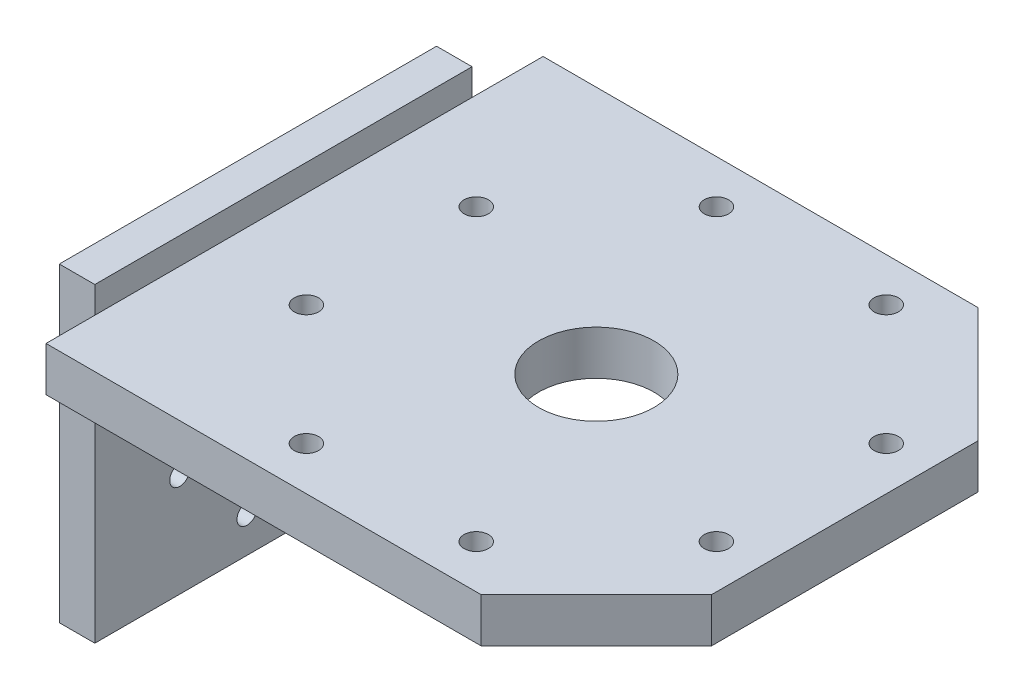
SolidWorks part; units mm, degrees
material "6061-T6 (SS)"
ref_plane "Front Plane" through (0, 0, 0) normal (0, 0, 1) x (1, 0, 0)
ref_plane "Top Plane" through (0, 0, 0) normal (0, 1, 0) x (1, 0, 0)
ref_plane "Right Plane" through (0, 0, 0) normal (1, 0, 0) x (0, 0, -1)
ref_plane "PL_Back_Plate_base" through (-76, 0, 0) normal (1, 0, 0) x (0, 0, -1)
sketch "SK_Back_Plate" plane through (-76, 0, 0) normal (1, 0, 0) x (0, 0, -1)
  line L0 (40, 36) -> (40, -34)
  line L1 (40, -34) -> (-45, -34)
  line L2 (-45, -34) -> (-45, 36)
  line L3 (-45, 36) -> (40, 36)
  circle A0 centre (25.8686, -10.7151) radius 2.25
  circle A1 centre (10.7151, -25.8686) radius 2.25
  circle A2 centre (-10.7151, -25.8686) radius 2.25
  circle A3 centre (-25.8686, -10.7151) radius 2.25
  circle A4 centre (-25.8686, 10.7151) radius 2.25
  circle A5 centre (-10.7151, 25.8686) radius 2.25
  circle A6 centre (10.7151, 25.8686) radius 2.25
  circle A7 centre (25.8686, 10.7151) radius 2.25
  circle A8 centre (0, 0) radius 6
  dimension "D9_SK_Back_Plate" = 4.5
  dimension "D12_SK_Back_Plate" = 4.5
  dimension "D15_SK_Back_Plate" = 4.5
  dimension "D18_SK_Back_Plate" = 4.5
  dimension "D21_SK_Back_Plate" = 4.5
  dimension "D24_SK_Back_Plate" = 4.5
  dimension "D27_SK_Back_Plate" = 4.5
  dimension "D30_SK_Back_Plate" = 4.5
  dimension "D33_SK_Back_Plate" = 12
  dimension "P1" = 40
  dimension "P2" = 36
  dimension "P3" = 40
  dimension "P4" = 34
  dimension "P5" = 45
  dimension "P6" = 34
  dimension "P7" = 45
  dimension "P8" = 36
  dimension "P10" = 25.8686
  dimension "P11" = 10.7151
  dimension "P13" = 10.7151
  dimension "P14" = 25.8686
  dimension "P16" = 10.7151
  dimension "P17" = 25.8686
  dimension "P19" = 25.8686
  dimension "P20" = 10.7151
  dimension "P22" = 25.8686
  dimension "P23" = 10.7151
  dimension "P25" = 10.7151
  dimension "P26" = 25.8686
  dimension "P28" = 10.7151
  dimension "P29" = 25.8686
  dimension "P31" = 25.8686
  dimension "P32" = 10.7151
extrude "Back_Plate" add sketch "SK_Back_Plate" along normal blind 8
ref_plane "PL_Roll_Pilot_Recess_base" through (-76, 0, 0) normal (1, 0, 0) x (0, 0, -1)
sketch "SK_Roll_Pilot_Recess" plane through (-76, 0, 0) normal (1, 0, 0) x (0, 0, -1)
  circle A0 centre (0, 0) radius 22.15
  dimension "D1_SK_Roll_Pilot_Recess" = 44.3
extrude "Roll_Pilot_Recess" cut sketch "SK_Roll_Pilot_Recess" along normal blind 2.2
ref_plane "PL_Medial_Plate_base" through (0, 20, 0) normal (0, 1, 0) x (1, 0, 0)
sketch "SK_Medial_Plate" plane through (0, 20, 0) normal (0, 1, 0) x (1, 0, 0)
  line L0 (-68, 56) -> (30, 56)
  line L1 (30, 56) -> (56, 30)
  line L2 (56, 30) -> (56, -30)
  line L3 (56, -30) -> (30, -56)
  line L4 (30, -56) -> (-68, -56)
  line L5 (-68, -56) -> (-68, 56)
  circle A0 centre (46.194, 19.1342) radius 2.75
  circle A1 centre (19.1342, 46.194) radius 2.75
  circle A2 centre (-19.1342, 46.194) radius 2.75
  circle A3 centre (-46.194, 19.1342) radius 2.75
  circle A4 centre (-46.194, -19.1342) radius 2.75
  circle A5 centre (-19.1342, -46.194) radius 2.75
  circle A6 centre (19.1342, -46.194) radius 2.75
  circle A7 centre (46.194, -19.1342) radius 2.75
  circle A8 centre (0, 0) radius 13
  dimension "D13_SK_Medial_Plate" = 5.5
  dimension "D16_SK_Medial_Plate" = 5.5
  dimension "D19_SK_Medial_Plate" = 5.5
  dimension "D22_SK_Medial_Plate" = 5.5
  dimension "D25_SK_Medial_Plate" = 5.5
  dimension "D28_SK_Medial_Plate" = 5.5
  dimension "D31_SK_Medial_Plate" = 5.5
  dimension "D34_SK_Medial_Plate" = 5.5
  dimension "D37_SK_Medial_Plate" = 26
  dimension "P1" = 68
  dimension "P2" = 56
  dimension "P3" = 30
  dimension "P4" = 56
  dimension "P5" = 56
  dimension "P6" = 30
  dimension "P7" = 56
  dimension "P8" = 30
  dimension "P9" = 30
  dimension "P10" = 56
  dimension "P11" = 68
  dimension "P12" = 56
  dimension "P14" = 46.194
  dimension "P15" = 19.1342
  dimension "P17" = 19.1342
  dimension "P18" = 46.194
  dimension "P20" = 19.1342
  dimension "P21" = 46.194
  dimension "P23" = 46.194
  dimension "P24" = 19.1342
  dimension "P26" = 46.194
  dimension "P27" = 19.1342
  dimension "P29" = 19.1342
  dimension "P30" = 46.194
  dimension "P32" = 19.1342
  dimension "P33" = 46.194
  dimension "P35" = 46.194
  dimension "P36" = 19.1342
extrude "Medial_Plate" add sketch "SK_Medial_Plate" along normal blind 10
equation "\"Roll_face_x\"= -76"
equation "\"Pitch_rear_y\"= -20"
equation "\"Plate_t\"= 10"
equation "\"Back_bottom_z\"= -40"
